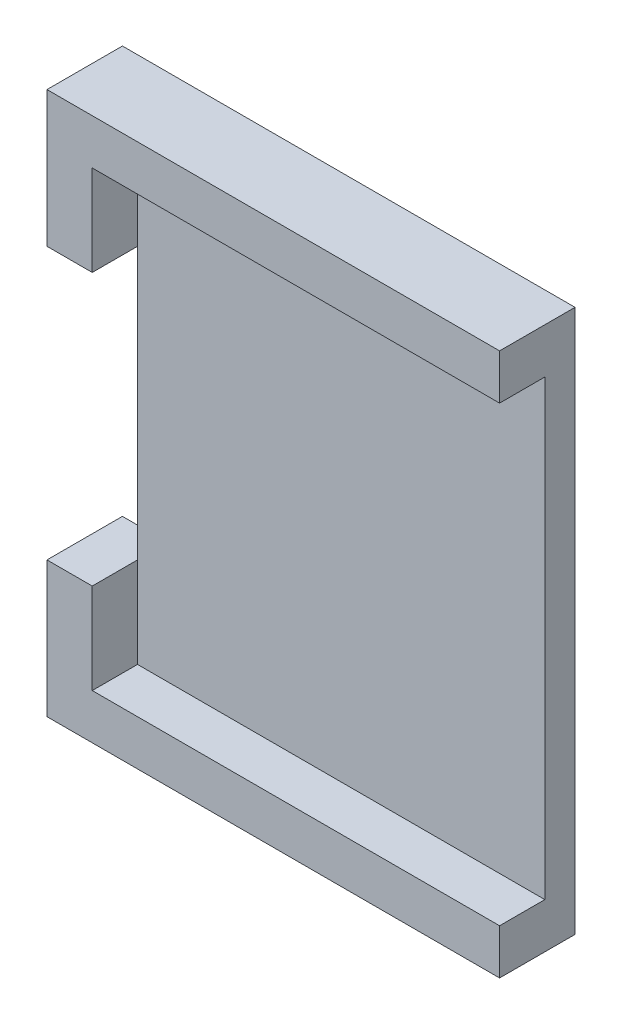
SolidWorks part; units mm, degrees
ref_plane "Front Plane" through (0, 0, 0) normal (0, 0, 1) x (1, 0, 0)
ref_plane "Top Plane" through (0, 0, 0) normal (0, 1, 0) x (1, 0, 0)
ref_plane "Right Plane" through (0, 0, 0) normal (1, 0, 0) x (0, 0, -1)
sketch "Sketch1" plane through (0, 0, 0) normal (0, 0, 1) x (1, 0, 0)
  line L0 (-12, 9) -> (-12, -9)
  line L1 (15, 15) -> (-15, 15)
  line L2 (15, 15) -> (15, -15)
  line L3 (15, -15) -> (-15, -15)
  line L4 (-15, 15) -> (-15, -15)
  line L5 (15, 15) -> (-15, -15) construction
  line L6 (15, -15) -> (-15, 15) construction
  line L7 (-15, 15) -> (-12, 15)
  line L8 (-15, 15) -> (-15, 9)
  line L9 (-15, 9) -> (-12, 9)
  line L10 (-12, 15) -> (-12, 9)
  line L11 (-15, -15) -> (-12, -15)
  line L12 (-15, -15) -> (-15, -9)
  line L13 (-15, -9) -> (-12, -9)
  line L14 (-12, -15) -> (-12, -9)
  line L16 (-15, -15) -> (15, -15)
  line L17 (-15, -15) -> (-15, -18)
  line L18 (-15, -18) -> (15, -18)
  line L19 (15, -15) -> (15, -18)
  line L20 (15, 15) -> (-15, 15)
  line L21 (15, 15) -> (15, 18)
  line L22 (15, 18) -> (-15, 18)
  line L23 (-15, 15) -> (-15, 18)
  point P0 (0, 0)
  point P17 (14.7481, -15)
  point P18 (-15.2385, 15)
  dimension "D1" = 18
  dimension "D2" = 30
  dimension "D3" = 30
  dimension "D4" = 3
extrude "Boss-Extrude1" add sketch "Sketch1" along normal blind 2 contours L14 L3 L2 L1 L10 L0 | L10 L1 L4 L9 | L3 L14 L13 L4 | L23 L1 L21 L22 | L19 L3 L17 L18 region at (1.5, 0, 0) region at (-13.5, 12, 0) region at (-13.5, -12, 0) region at (0, 16.5, 0) region at (0, -16.5, 0)
extrude "Boss-Extrude2" add sketch "Sketch1<3>" along normal blind 5 contours L10 L1 L4 L9 | L23 L1 L21 L22 | L3 L14 L13 L4 | L19 L3 L17 L18 region at (-13.5, 12, 0) region at (-13.5, -12, 0) region at (0, 16.5, 0) region at (0, -16.5, 0)
sketch "Sketch1<3>" plane through (0, 0, 0) normal (0, 0, 1) x (1, 0, 0) same geometry as "Sketch1"
